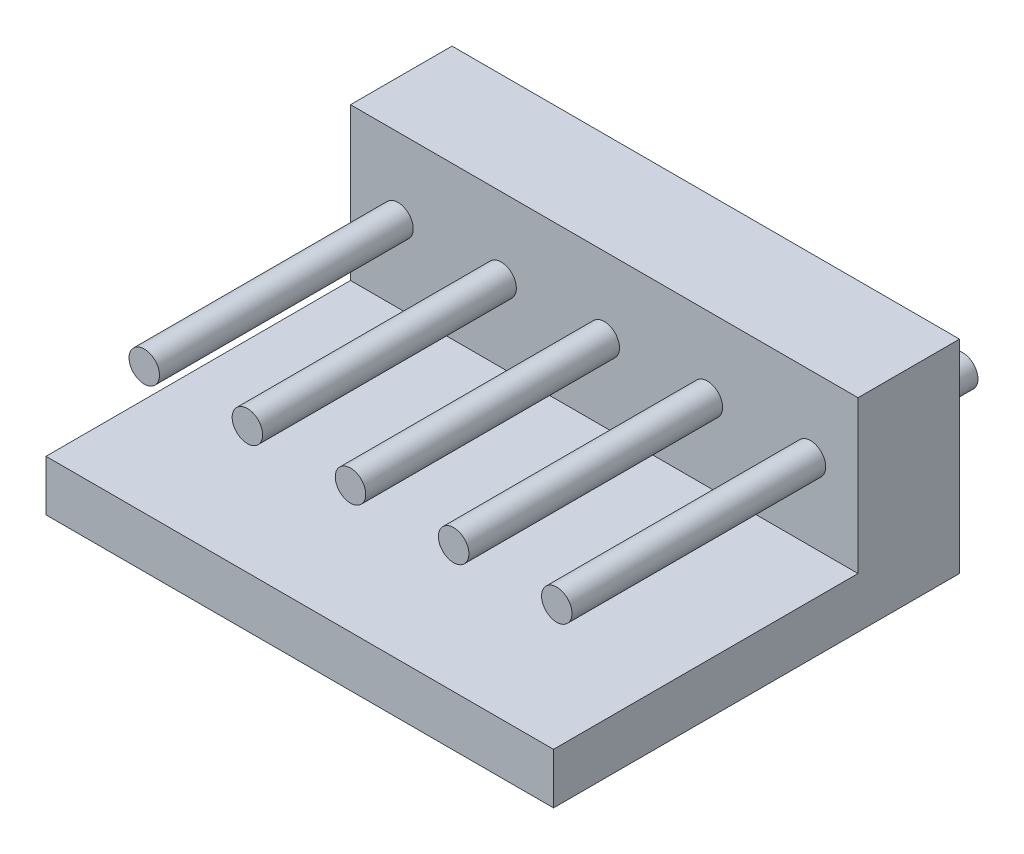
SolidWorks part; units mm, degrees
ref_plane "Спереди" through (0, 0, 0) normal (0, 0, 1) x (1, 0, 0)
ref_plane "Сверху" through (0, 0, 0) normal (0, 1, 0) x (1, 0, 0)
ref_plane "Справа" through (0, 0, 0) normal (1, 0, 0) x (0, 0, -1)
sketch "Эскиз1" plane through (0, 0, 0) normal (0, 0, 1) x (1, 0, 0)
  line L1 (0, 0) -> (25, 0)
  line L2 (0, 0) -> (0, 10)
  line L3 (0, 10) -> (25, 10)
  line L4 (25, 0) -> (25, 10)
  dimension "D1" = 25
  dimension "D2" = 10
extrude "Вытянуть1" add sketch "Эскиз1" along normal blind 5
sketch "Эскиз2" plane through (0, 0, 5) normal (0, 0, 1) x (1, 0, 0)
  line L1 (25, 0) -> (25, 10) construction
  line L2 (0, 0) -> (25, 0)
  line L3 (0, 0) -> (0, 2.5)
  line L4 (0, 2.5) -> (25, 2.5)
  line L7 (25, 0) -> (25, 2.5)
  dimension "D1" = 2.5
extrude "Вытянуть2" add sketch "Эскиз2" along normal blind 15
sketch "Эскиз3" plane through (0, 0, 5) normal (0, 0, 1) x (1, 0, 0)
  line L3 (12.5, 12.0229) -> (12.5, -0.8356) construction
  line L4 (0, 10) -> (0, 2.5) construction
  line L5 (25, 2.5) -> (25, 10) construction
  line L7 (12.5, 6.25) -> (22.66, 6.25) construction
  line L9 (25, 10) -> (0, 10) construction
  circle A0 centre (17.58, 6.25) radius 0.75
  circle A1 centre (22.66, 6.25) radius 0.75
  circle A2 centre (2.34, 6.25) radius 0.75
  circle A3 centre (7.42, 6.25) radius 0.75
  circle A4 centre (12.5, 6.25) radius 0.75
  dimension "D1" = 20.32
  dimension "D2" = 1.5
  dimension "D3" = 3.75
  dimension "D4" = 10.16
extrude "Вытянуть3" add sketch "Эскиз3" along normal blind 12.5 and the other way blind 7.5
